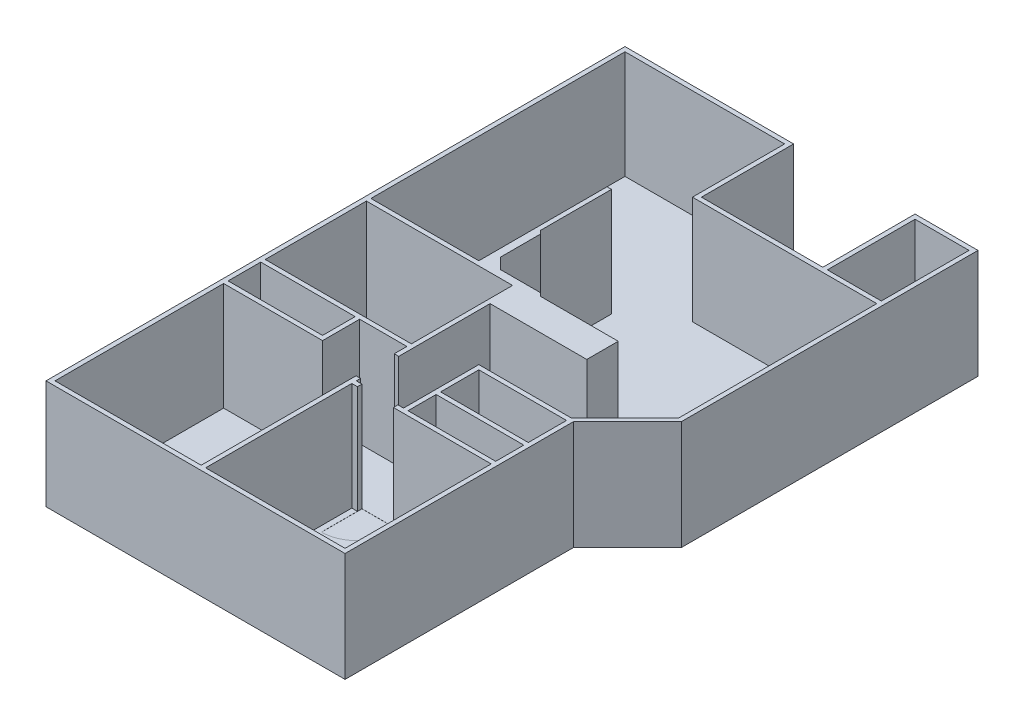
SolidWorks part; units mm, degrees
ref_plane "Front Plane" through (0, 0, 0) normal (0, 0, 1) x (1, 0, 0)
ref_plane "Top Plane" through (0, 0, 0) normal (0, 1, 0) x (1, 0, 0)
ref_plane "Right Plane" through (0, 0, 0) normal (1, 0, 0) x (0, 0, -1)
sketch "Sketch1" plane through (0, 0, 0) normal (0, 1, 0) x (1, 0, 0)
  line L0 (6553.2, 4038.6) -> (6553.2, 5105.4)
  line L1 (0, 0) -> (3302, 0)
  line L2 (0, 0) -> (0, 4648.2)
  line L3 (0, 4648.2) -> (3302, 4648.2)
  line L4 (3302, 0) -> (3302, 4648.2)
  line L5 (3403.6, 0) -> (6553.2, 0)
  line L6 (3403.6, 0) -> (3403.6, 3302)
  line L7 (4572, 4038.6) -> (6553.2, 4038.6)
  line L8 (6553.2, 0) -> (6553.2, 3302)
  line L9 (0, 4749.8) -> (3302, 4749.8)
  line L10 (0, 4749.8) -> (0, 7035.8)
  line L11 (0, 7035.8) -> (3302, 7035.8)
  line L12 (3302, 4749.8) -> (3302, 7035.8)
  line L13 (0, 7137.4) -> (2438.4, 7137.4)
  line L14 (0, 7137.4) -> (0, 10033)
  line L15 (0, 10033) -> (2438.4, 10033) construction
  line L16 (2438.4, 7137.4) -> (2438.4, 10033)
  line L18 (0, 10134.6) -> (0, 12877.8)
  line L19 (0, 12877.8) -> (3606.8, 12877.8)
  line L20 (3606.8, 10795) -> (3606.8, 12877.8)
  line L21 (3708.4, 10896.6) -> (6451.6, 10896.6)
  line L22 (3708.4, 10896.6) -> (3708.4, 13335)
  line L23 (3708.4, 13335) -> (6451.6, 13335)
  line L24 (6451.6, 10896.6) -> (6451.6, 13335)
  line L25 (2540, 7137.4) -> (7772.4, 7137.4)
  line L26 (2540, 7137.4) -> (2540, 10033)
  line L27 (3606.8, 10795) -> (7772.4, 10795)
  line L28 (7772.4, 7137.4) -> (7772.4, 10795)
  line L29 (6553.2, 5105.4) -> (7772.4, 6324.6)
  line L30 (7772.4, 6324.6) -> (7772.4, 7137.4)
  line L31 (431.8, 5359.4) -> (431.8, 4749.8) construction
  line L32 (6553.2, 10896.6) -> (7772.4, 10896.6)
  line L33 (6553.2, 10896.6) -> (6553.2, 12877.8)
  line L34 (6553.2, 12877.8) -> (7772.4, 12877.8)
  line L35 (7772.4, 10896.6) -> (7772.4, 12877.8)
  line L36 (16.81, 5504.4208) -> (778.81, 5504.4208) construction
  line L37 (16.81, 5504.4208) -> (16.81, 4590.0208) construction
  line L38 (16.81, 4590.0208) -> (778.81, 4590.0208) construction
  line L39 (778.81, 5504.4208) -> (778.81, 4590.0208) construction
  line L40 (0, 7035.8) -> (1651, 7035.8)
  line L41 (0, 7035.8) -> (0, 6426.2)
  line L42 (0, 6426.2) -> (1651, 6426.2)
  line L43 (1651, 7035.8) -> (1651, 6426.2)
  line L44 (1651, 6578.6) -> (3302, 6578.6)
  line L45 (1651, 6578.6) -> (1651, 7035.8)
  line L46 (1651, 7035.8) -> (3302, 7035.8)
  line L47 (3302, 6578.6) -> (3302, 7035.8)
  line L48 (170.0343, 4749.8) -> (693.5657, 4749.8)
  line L49 (170.0343, 4749.8) -> (170.0343, 5359.4)
  line L50 (170.0343, 5359.4) -> (693.5657, 5359.4)
  line L51 (693.5657, 4749.8) -> (693.5657, 5359.4)
  line L52 (0, 6248.4) -> (1524, 6248.4) construction
  line L53 (1524, 6248.4) -> (1524, 4749.8) construction
  line L54 (0, 5664.2) -> (1651, 5664.2) construction
  line L55 (1651, 5664.2) -> (1651, 6426.2) construction
  line L56 (2540, 8430.5569) -> (3833.1569, 7137.4)
  line L57 (5588, 7137.4) -> (5588, 6426.2)
  line L58 (5588, 6426.2) -> (3302, 6426.2)
  line L59 (6553.2, 5105.4) -> (4470.4, 5105.4)
  line L60 (4470.4, 5105.4) -> (4470.4, 3403.6)
  line L61 (3403.6, -101.6) -> (6654.8, -101.6) construction
  line L62 (-101.6, -101.6) -> (-101.6, 12979.4)
  line L63 (-101.6, -101.6) -> (6654.8, -101.6)
  line L64 (6654.8, -101.6) -> (6654.8, 5063.3159)
  line L65 (6654.8, 5063.3159) -> (7874, 6282.5159)
  line L66 (7874, 6282.5159) -> (7874, 7137.4)
  line L67 (7874, 7137.4) -> (7874, 12979.4)
  line L68 (-101.6, 12979.4) -> (3708.4, 12979.4)
  line L69 (-101.6, -101.6) -> (-101.6, 4648.2) construction
  line L70 (0, 12979.4) -> (3606.8, 12979.4) construction
  line L71 (7874, 7137.4) -> (7874, 10795) construction
  line L72 (6451.6, 12979.4) -> (7874, 12979.4)
  line L73 (6654.8, -101.6) -> (6654.8, 4038.6) construction
  line L74 (3302, 3499.2131) -> (3403.6, 3499.2131)
  line L75 (6625.042, 5033.558) -> (7874, 6282.5159) construction
  line L76 (-101.6, -101.6) -> (3302, -101.6) construction
  line L77 (3403.6, 3403.6) -> (3403.6, 6426.2)
  line L78 (0, 3911.6) -> (2133.6, 3911.6)
  line L79 (2133.6, 3911.6) -> (2133.6, 4648.2)
  line L80 (2235.2, 4648.2) -> (2235.2, 3810)
  line L81 (2235.2, 3810) -> (0, 3810)
  line L82 (3302, 4362.8131) -> (3403.6, 4362.8131)
  line L83 (4572, 3403.6) -> (6553.2, 3403.6)
  line L84 (0, 10134.6) -> (0, 10033)
  line L85 (3403.6, 3302) -> (6553.2, 3302)
  line L86 (3403.6, 3403.6) -> (4470.4, 3403.6)
  line L87 (4572, 3403.6) -> (4572, 4038.6)
  line L88 (2438.4, 10033) -> (2540, 10033)
  line L89 (4572, 4140.2) -> (6553.2, 4140.2)
  line L90 (6553.2, 3403.6) -> (6553.2, 4038.6)
  line L92 (4572, 4140.2) -> (4572, 5003.8)
  line L93 (4572, 5003.8) -> (6553.2, 5003.8)
  line L95 (6553.2, 0) -> (6553.2, 4038.6) construction
  dimension "D1" = 3302
  dimension "D3" = 3149.6
  dimension "D5" = 101.6
  dimension "D6" = 101.6
  dimension "D7" = 101.6
  dimension "D8" = 2895.6
  dimension "D9" = 2438.4
  dimension "D10" = 3810
  dimension "D11" = 2743.2
  dimension "D12" = 3606.8
  dimension "D13" = 101.6
  dimension "D14" = 2743.2
  dimension "D15" = 2438.4
  dimension "D16" = 5232.4
  dimension "D17" = 3657.6
  dimension "D18" = 101.6
  dimension "D19" = 101.6
  dimension "D20" = 45
  dimension "D21" = 101.6
  dimension "D22" = 914.4
  dimension "D23" = 762
  dimension "D24" = 431.8
  dimension "D25" = 1498.6
  dimension "D26" = 2286
  dimension "D27" = 762
  dimension "D28" = 609.6
  dimension "D29" = 609.6
  dimension "D30" = 152.4
  dimension "D31" = 45
  dimension "D32" = 1828.8
  dimension "D33" = 2286
  dimension "D34" = 1066.8
  dimension "D35" = 2082.8
  dimension "D37" = 863.6
  dimension "D40" = 101.6
  dimension "D41" = 101.6
  dimension "D42" = 101.6
  dimension "D43" = 736.6
  dimension "D44" = 736.6
  dimension "D45" = 3302
  dimension "D46" = 1066.8
  dimension "D47" = 101.6
  dimension "D48" = 101.6
  dimension "D49" = 101.6
  dimension "D50" = 101.6
  dimension "D36" = 101.6
  dimension "D38" = 101.6
  dimension "D39" = 101.6
extrude "Boss-Extrude2" add sketch "Sketch1" along normal blind 2438.4 contours L81 L80 L3 L79 L78 L2 | L72 L24 L21 L22 L68 L62 L63 L64 L65 L66 L67 L86 L77 L74 L4 L1 L2 L3 L82 L12 L9 L10 L11 L58 L57 L25 L26 L18 L19 L20 L27 L28 L30 | L56 L26 L25 region at (2971.0523, 0, -7568.4523) region at (23.8719, 0, -3860.8) region at (5080, 0, -10881.2793)
extrude "Boss-Extrude3" add sketch "Sketch1<5>" against normal blind 25.4 contours L21 L24 L23 L22 | L32 L35 L34 L33 | L72 L24 L21 L22 L68 L62 L63 L64 L65 L66 L67 L88 L16 L13 L14 L84 L18 L19 L20 L27 L28 L30 L29 L8 L5 L6 L85 L59 L60 L86 L77 L74 L4 L1 L2 L3 L82 L12 | L16 L88 L26 L56 L25 L28 L27 L20 L19 L18 L84 L14 L13 | L77 L86 L60 L59 L29 L30 L25 L57 L58 | L51 L9 L12 L44 L43 L42 L10 L49 L50 | L43 L44 L12 L11 | L43 L11 L10 L42 | L9 L51 L50 L49 | L78 L79 L3 L2 | L81 L80 L3 L79 L78 L2 | L80 L81 L2 L1 L4 L3 | L82 L4 L74 L77 | L85 L6 L5 L8 | L56 L26 L25 | L93 L92 L89 L0 | L83 L90 L7 L87 region at (1760.1466, 0, -5661.2097) region at (5275.7092, 0, -5649.4897) region at (5562.6, 0, -4572) region at (5562.6, 0, -3721.1) region at (3470.5083, 0, -9622.3981) region at (2971.0523, 0, -7568.4523) region at (3352.8, 0, -3931.0131) region at (1725.1642, 0, -2059.2278) region at (2476.5, 0, -6807.2) region at (431.8, 0, -5054.6) region at (825.5, 0, -6731) region at (23.8719, 0, -3860.8) region at (1066.8, 0, -4279.9) region at (4978.4, 0, -1651) region at (5080, 0, -12115.8) region at (5080, 0, -10881.2793) region at (7162.8, 0, -11887.2)
sketch "Sketch1<5>" plane through (0, 0, 0) normal (0, 1, 0) x (1, 0, 0) same geometry as "Sketch1"
sketch "Sketch2" plane through (0, 2438.4, 0) normal (0, 1, 0) x (1, 0, 0)
  line L0 (3937, 3403.6) -> (3937, 3302) construction
  line L1 (3403.6, 3403.6) -> (4470.4, 3403.6) construction
  line L2 (3403.6, 3302) -> (6553.2, 3302) construction
  line L3 (3530.6, 3403.6) -> (3530.6, 3302)
  line L4 (4343.4, 3403.6) -> (4343.4, 3302)
  line L5 (3530.6, 3403.6) -> (4343.4, 3403.6)
  line L6 (3530.6, 3302) -> (4343.4, 3302) construction
  line L7 (3530.6, 3302) -> (3530.6, 2489.2)
  arc A0 (4343.4, 3302) -> (3530.6, 2489.2) centre (3530.6, 3302) cw
  dimension "D1" = 406.4
  dimension "D2" = 406.4
extrude "Cut-Extrude1" cut sketch "Sketch2" against normal offset from surface (2440.94 mm away) 2.54 up to face at (4978.4, 0, -1651) offset beyond the face yes
sketch "Sketch3" plane through (0, 2438.4, 0) normal (0, 1, 0) x (1, 0, 0)
  line L0 (2611.842, 8358.7148) -> (2611.842, 7457.0148)
  line L1 (2540, 8430.5569) -> (3833.1569, 7137.4) construction
  line L2 (2611.842, 7457.0148) -> (2859.6148, 7209.242)
  line L3 (2859.6148, 7209.242) -> (3761.3148, 7209.242)
  line L4 (3761.3148, 7209.242) -> (2611.842, 8358.7148)
  line L5 (3186.5784, 7783.9784) -> (2438.4, 7035.8) construction
  line L6 (2540, 8430.5569) -> (3833.1569, 7137.4) construction
  line L7 (0, 7035.8) -> (3302, 7035.8) construction
  dimension "D1" = 1625.6
  dimension "D2" = 901.7
extrude "Cut-Extrude2" cut sketch "Sketch3" against normal offset from surface (1168.4 mm away) 1270 up to face at (3412.8386, 0, -6001.147)
sketch "Sketch4" plane through (0, 0, 0) normal (0, 1, 0) x (1, 0, 0)
  circle A0 centre (7295.9701, 10488.3514) radius 127
  dimension "D1" = 254
extrude "Boss-Extrude4" add sketch "Sketch4" along normal blind 914.4
